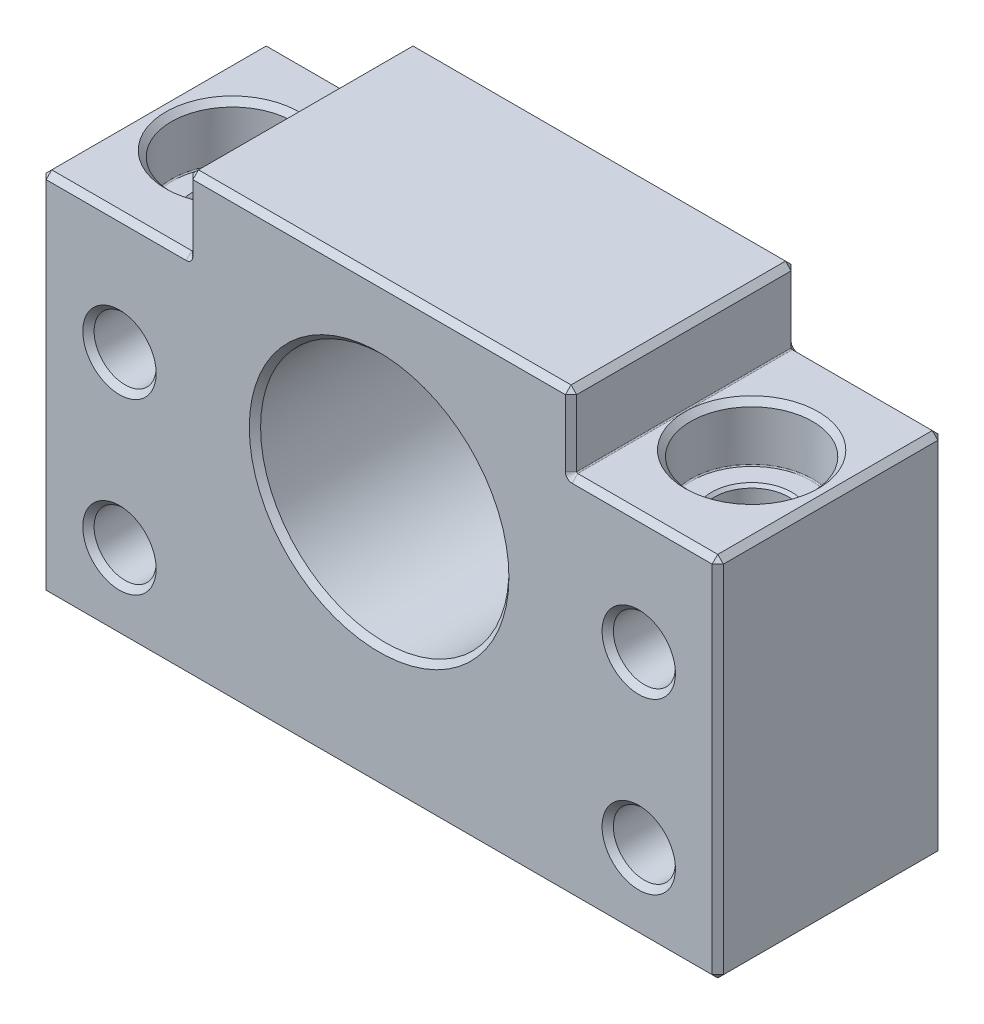
SolidWorks part; units mm, degrees
material "1023 Carbon Steel Sheet (SS)"
ref_plane "Front Plane" through (0, 0, 0) normal (0, 0, 1) x (1, 0, 0)
ref_plane "Top Plane" through (0, 0, 0) normal (0, 1, 0) x (1, 0, 0)
ref_plane "Right Plane" through (0, 0, 0) normal (1, 0, 0) x (0, 0, -1)
sketch "BF Body Sketch" plane through (0, 0, 0) normal (0, 0, 1) x (1, 0, 0)
  line L0 (30, -22) -> (-30, -22)
  line L1 (-30, -22) -> (-30, 10.5)
  line L2 (-30, 10.5) -> (-17, 10.5)
  line L3 (-17, 10.5) -> (-17, 17)
  line L4 (-17, 17) -> (17, 17)
  line L5 (17, 17) -> (17, 10.5)
  line L6 (17, 10.5) -> (30, 10.5)
  line L7 (30, 10.5) -> (30, -22)
  point P2 (0, -22)
  point P3 (0, 17)
  dimension "B" = 60
  dimension "H2" = 22
  dimension "H1" = 32.5
  dimension "B1" = 34
  dimension "H" = 39
extrude "BF Body" add sketch "BF Body Sketch" along normal mid plane 20
sketch "Ball Bearing Hole Sketch" plane through (0, 0, 0) normal (0, 0, 1) x (1, 0, 0)
  circle A4 centre (0, 0) radius 11
  dimension "DO" = 22
extrude "Ball Bearing Hole" cut sketch "Ball Bearing Hole Sketch" against normal through all both and the other way through all
hole_wizard "Vertical Holes" positions "Sketch1" profile "Sketch2" counterbore size "M6" standard "ISO" end condition through all
sketch "Sketch1" plane through (0, 10.5, 0) normal (0, 1, 0) x (1, 0, 0)
  line L0 (23, 0) -> (-23, 0) construction
  point P0 (-23, 0)
  point P2 (23, 0)
  point P9 (0, 0)
  dimension "P" = 46
sketch "Sketch2" plane through (-23, 10.5, 0) normal (1, 0, 0) x (0, 0, 1)
  line L0 (0, 0) -> (0, 32.5)
  line L1 (3.3, 32) -> (3.8, 32.5)
  line L2 (3.3, 32) -> (3.3, 5.25)
  line L3 (3.3, 5.25) -> (3.55, 5)
  line L4 (3.55, 5) -> (5.4, 5)
  line L5 (5.4, 5) -> (5.4, 0.5)
  line L6 (5.4, 0.5) -> (5.9, 0)
  line L7 (5.9, 0) -> (0, 0)
  line L8 (-5.4, 0.5) -> (-5.9, 0) construction
  line L9 (-3.3, 5.25) -> (-3.55, 5) construction
  line L11 (0, -6.35) -> (0, 107.95) construction
  line L12 (3.8, 32.5) -> (0, 32.5)
  line L13 (-3.3, 32) -> (-3.8, 32.5) construction
  dimension "Near C'Sink Angle" = 90
  dimension "Far C'Sink Angle" = 90
  dimension "Thru Hole Dia." = 6.6
  dimension "Thru Hole Depth" = 32.5
  dimension "C'Bore Dia." = 10.8
  dimension "C'Bore Depth" = 5
  dimension "Near C'Sink Dia." = 11.8
  dimension "Mid C'Sink Dia." = 7.1
  dimension "Mid C'Sink Angle" = 90
  dimension "Far C'Sink Dia." = 7.6
hole_wizard "Horizontal Holes" positions "Sketch3" profile "Sketch4" hole size "M5" standard "ISO" end condition through all
sketch "Sketch3" plane through (0, 0, 10) normal (0, 0, 1) x (1, 0, 0)
  line L0 (23, 0) -> (-23, 0) construction
  point P0 (-23, 0)
  point P2 (23, 0)
  point P4 (23, -15)
  point P6 (-23, -15)
  point P12 (0, 0)
  dimension "P" = 46
  dimension "E" = 15
sketch "Sketch4" plane through (-23, 0, 10) normal (1, 0, 0) x (0, -1, 0)
  line L0 (0, 0) -> (0, 20)
  line L1 (0, 20) -> (3.25, 20)
  line L2 (2.75, 19.5) -> (2.75, 0.5)
  line L3 (2.75, 0.5) -> (3.25, 0)
  line L5 (3.25, 0) -> (0, 0)
  line L6 (-2.75, 0.5) -> (-3.25, 0) construction
  line L7 (3.25, 20) -> (2.75, 19.5)
  line L8 (-3.25, 20) -> (-2.75, 19.5) construction
  line L11 (0, -6.35) -> (0, 107.95) construction
  dimension "Thru Hole Dia." = 5.5
  dimension "Thru Hole Depth" = 20
  dimension "Near C'Sink Dia." = 6.5
  dimension "Near C'Sink Angle" = 90
  dimension "Far C'Sink Dia." = 6.5
  dimension "Far C'Sink Angle" = 90
fillet "Production Filet" radius 0.1 4 edges at (-17, 10.5, 0) (17, 10.5, 0) (-23, 5.5, 5.4) (23, 5.5, 5.4)
chamfer "Aesthetic Chamfer" distance 0.5 angle 45 28 edges at (11, 0, -10) (17, 17, 0) (-17, 17, 0) (30, 10.5, 0) (-30, 10.5, 0) (-30, -22, 0) (23.55, 10.5, -10) (17.0293, 10.5293, -10) (17, 13.8, -10) (0, 17, -10) (-17, 13.8, -10) (-17.0293, 10.5293, -10) (-23.55, 10.5, -10) (-30, -5.75, -10) (0, -22, -10) (30, -5.75, -10) (30, -22, 0) (0, -22, 10) (-30, -5.75, 10) (-23.55, 10.5, 10) (-17.0293, 10.5293, 10) (-17, 13.8, 10) (0, 17, 10) (17, 13.8, 10) (17.0293, 10.5293, 10) (23.55, 10.5, 10) (30, -5.75, 10) (11, 0, 10)
equation "\"Near C'Sink Dia.@Sketch4\"= \"Thru Hole Dia.@Sketch4\" + 1"
equation "\"Far C'Sink Dia.@Sketch4\"= \"Thru Hole Dia.@Sketch4\" + 1"
equation "\"Near C'Sink Dia.@Sketch2\"= \"C'Bore Dia.@Sketch2\" + 1"
equation "\"Mid C'Sink Dia.@Sketch2\"= \"Thru Hole Dia.@Sketch2\" + 0.5"
equation "\"Far C'Sink Dia.@Sketch2\"= \"Thru Hole Dia.@Sketch2\" + 1"
